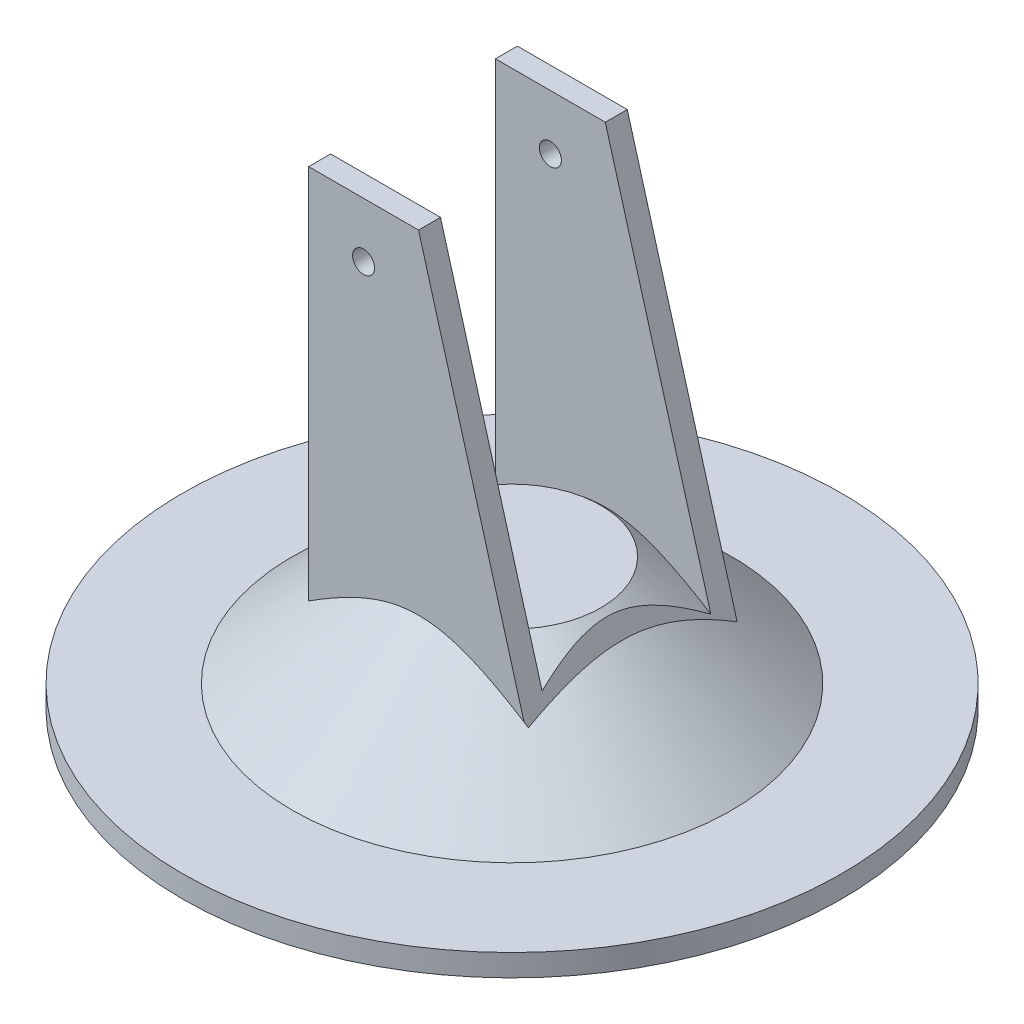
SolidWorks part; units mm, degrees
ref_plane "Front Plane" through (0, 0, 0) normal (0, 0, 1) x (1, 0, 0)
ref_plane "Top Plane" through (0, 0, 0) normal (0, 1, 0) x (1, 0, 0)
ref_plane "Right Plane" through (0, 0, 0) normal (1, 0, 0) x (0, 0, -1)
sketch "Sketch1" plane through (0, 0, 0) normal (0, 1, 0) x (1, 0, 0)
  circle A0 centre (0, -0.986) radius 30
  dimension "D1" = 60
extrude "Boss-Extrude1" add sketch "Sketch1" along normal blind 2
sketch "Sketch2" plane through (0, 2, 0) normal (0, 1, 0) x (1, 0, 0)
  circle A2 centre (0, -0.986) radius 20
  circle A3 centre (0, -0.986) radius 20
  dimension "D1" = 10
extrude "Boss-Extrude2" add sketch "Sketch2" along normal blind 10 draft 50
sketch "Sketch3" plane through (0, 2, 0) normal (0, 1, 0) x (1, 0, 0)
  line L1 (-10, -9.5) -> (10, -9.5)
  line L2 (-10, -9.5) -> (-10, 9.5)
  line L3 (-10, 9.5) -> (10, 9.5)
  line L4 (10, -9.5) -> (10, 9.5)
  line L5 (-10, -9.5) -> (10, 9.5) construction
  line L6 (-10, 9.5) -> (10, -9.5) construction
  line L7 (10, 9.5) -> (-10, 9.5)
  line L8 (10, 9.5) -> (10, 7.5)
  line L9 (10, 7.5) -> (-10, 7.5)
  line L10 (-10, 9.5) -> (-10, 7.5)
  line L11 (10, -9.5) -> (-10, -9.5)
  line L12 (10, -9.5) -> (10, -7.5)
  line L13 (10, -7.5) -> (-10, -7.5)
  line L14 (-10, -9.5) -> (-10, -7.5)
  point P0 (0, 0)
  dimension "D1" = 19
  dimension "D2" = 20
  dimension "D3" = 2
  dimension "D4" = 2
extrude "Boss-Extrude3" add sketch "Sketch3" along normal blind 40 contours L9 L4 L3 L2 | L4 L13 L2 L1 region at (0, 2, 8.5) region at (0, 2, -8.5)
sketch "Sketch5" plane through (0, 0, -9.5) normal (0, 0, -1) x (-1, 0, 0)
  line L0 (0, 42) -> (-10, 6.6235)
  line L1 (10, 42) -> (-10, 42) construction
  line L2 (-10, 6.6235) -> (-10, 42)
  line L3 (-10, 42) -> (0, 42)
extrude "Cut-Extrude1" cut sketch "Sketch5" against normal up to surface (19 mm away) up to face at (-0.4375, 25.8126, 9.5)
sketch "Sketch7" plane through (0, 0, -9.5) normal (0, 0, -1) x (-1, 0, 0)
  line L0 (10, 42) -> (0, 42) construction
  circle A0 centre (5, 37) radius 1
  point P4 (5, 42)
  dimension "D1" = 2
  dimension "D2" = 5
extrude "Cut-Extrude2" cut sketch "Sketch7" against normal up to surface (19 mm away) up to face at (-2.9865, 25.8436, 9.5)
